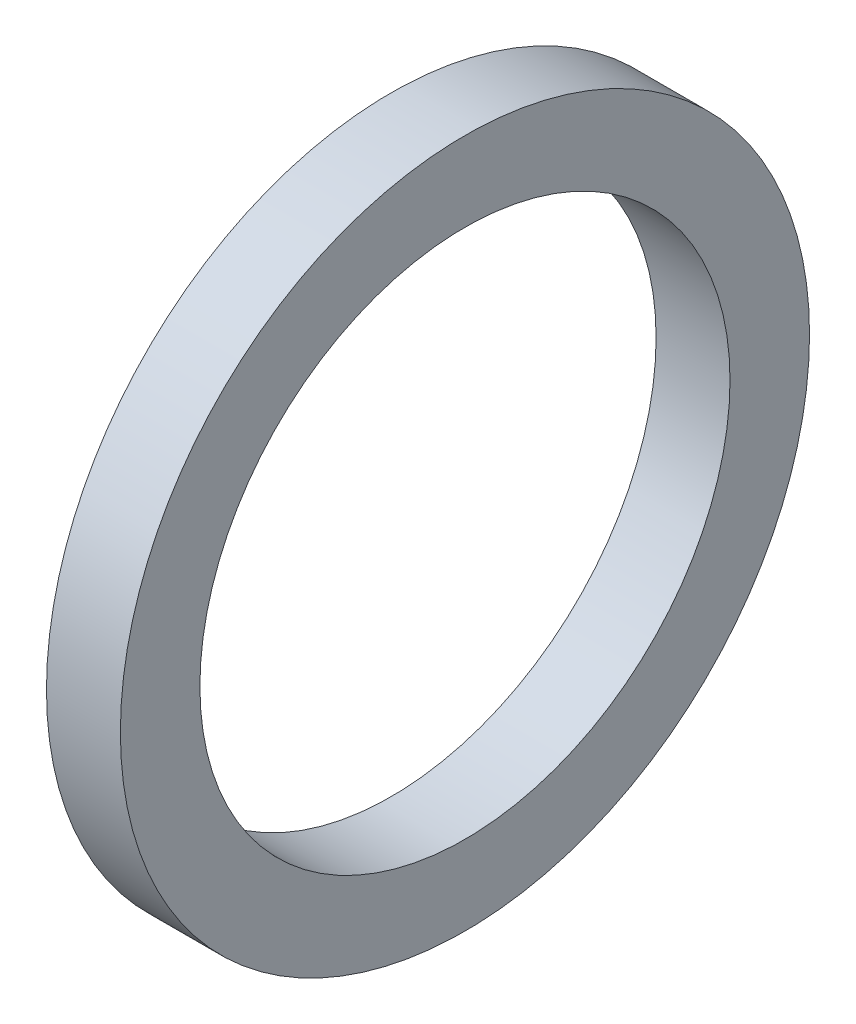
SolidWorks part; units mm, degrees
ref_plane "Front Plane" through (0, 0, 0) normal (0, 0, 1) x (1, 0, 0)
ref_plane "Top Plane" through (0, 0, 0) normal (0, 1, 0) x (1, 0, 0)
ref_plane "Right Plane" through (0, 0, 0) normal (1, 0, 0) x (0, 0, -1)
sketch "Sketch2" plane through (0, 0, 0) normal (0, 0, 1) x (1, 0, 0)
  line L0 (0, 0) -> (58.591, 0) construction
  line L2 (0, 0) -> (18.4, 0)
  line L3 (0, 0) -> (0, 2.5)
  line L4 (0, 2.5) -> (18.4, 2.5)
  line L5 (18.4, 0) -> (18.4, 2.5)
  line L6 (6, 2.5) -> (6, 6)
  line L11 (6, 6) -> (9.97, 6)
  line L16 (12.97, 6) -> (12.97, 3)
  line L17 (12.97, 3) -> (13.6304, 3)
  line L18 (13.6304, 3) -> (13.6304, 2.5)
  line L19 (13.6304, 2.5) -> (6, 2.5)
  line L22 (13.6304, 2.5) -> (16.1104, 2.5)
  line L23 (13.6304, 2.5) -> (13.6304, 4)
  line L24 (13.6304, 4) -> (16.1104, 4)
  line L25 (16.1104, 2.5) -> (16.1104, 4)
  line L27 (6, 6) -> (9.97, 6)
  line L28 (6, 6) -> (6, 9)
  line L29 (6, 9) -> (9.97, 9)
  line L30 (9.97, 6) -> (9.97, 9)
  line L31 (6, 9) -> (6, 8.25)
  line L32 (6, 8.25) -> (5, 8.25)
  line L33 (8.58, 22.001) -> (8.58, 12.476) construction
  line L34 (5, 12.476) -> (12.16, 12.476)
  line L35 (9.97, 9) -> (12.16, 9)
  line L36 (5, 7.5) -> (3, 7.5)
  line L37 (5, 8.25) -> (5, 12.476)
  line L38 (5, 7.5) -> (5, 14)
  line L39 (5, 14) -> (3, 14)
  line L40 (3, 7.5) -> (3, 14)
  line L41 (5, 22.001) -> (12.16, 22.001)
  line L42 (5, 22.001) -> (5, 30.1625)
  line L43 (5, 30.1625) -> (12.16, 30.1625)
  line L44 (12.16, 22.001) -> (12.16, 30.1625)
  line L49 (16.6304, 22.001) -> (16.6304, 7.5)
  line L51 (23.0104, 7.5) -> (23.0104, 6.5)
  line L54 (16.1104, 4) -> (13.6304, 4)
  line L56 (18.0304, 7.5) -> (23.0104, 7.5)
  line L57 (13.16, 22.001) -> (16.6304, 22.001)
  line L58 (16.1104, 3.5) -> (20.0104, 3.5)
  line L59 (29.9004, 14) -> (26.9004, 11)
  line L60 (4, 31.75) -> (18.0304, 31.75)
  line L61 (18.0304, 7.5) -> (23.0104, 7.5)
  line L62 (18.0304, 7.5) -> (18.0304, 12)
  line L63 (18.0304, 12) -> (23.0104, 12)
  line L64 (23.0104, 7.5) -> (23.0104, 12)
  line L65 (18.0304, 31.75) -> (18.0304, 12)
  line L66 (23.0104, 11) -> (26.9004, 11)
  line L67 (34.8004, 23) -> (31.3004, 19.5)
  line L68 (35.8004, 31) -> (38.7904, 33.99)
  line L69 (29.9004, 14) -> (29.9004, 15)
  line L70 (29.9004, 15) -> (22.9304, 15)
  line L71 (22.9304, 15) -> (21.0304, 15)
  line L72 (18.0304, 7.5) -> (16.6304, 7.5)
  line L73 (21.0304, 15) -> (21.0304, 43)
  line L74 (20.0304, 40) -> (10.0704, 40)
  line L75 (10.0704, 40) -> (4, 40)
  line L76 (21.0304, 43) -> (20.0304, 43)
  line L77 (22.9304, 15) -> (29.9004, 15)
  line L78 (22.9304, 15) -> (22.9304, 21)
  line L79 (22.9304, 21) -> (29.9004, 21)
  line L80 (29.9004, 15) -> (29.9004, 21)
  line L81 (10.0704, 40) -> (20.0304, 40)
  line L82 (10.0704, 40) -> (10.0704, 50)
  line L83 (10.0704, 50) -> (20.0304, 50)
  line L84 (20.0304, 40) -> (20.0304, 50)
  line L85 (4, 40) -> (4, 31.75)
  line L86 (12.97, 3) -> (12.97, 2.5)
  line L87 (31.3004, 19.5) -> (29.9004, 19.5)
  line L88 (21.51, 63.5) -> (21.51, 44)
  line L89 (21.51, 63.5) -> (25.9304, 63.5)
  line L90 (25.9304, 63.5) -> (25.9304, 25)
  line L91 (27.8304, 25) -> (25.9304, 25)
  line L92 (10.0704, 48) -> (9, 48)
  line L93 (9, 48) -> (9, 53.476)
  line L94 (9, 53.476) -> (20.0304, 53.476)
  line L95 (20.0304, 53.476) -> (20.0304, 50)
  line L96 (14.5152, 63.001) -> (14.5152, 53.476) construction
  line L97 (9, 63.001) -> (20.0304, 63.001)
  line L98 (9, 63.001) -> (9, 68.2625)
  line L99 (9, 68.2625) -> (20.0304, 68.2625)
  line L100 (20.0304, 63.001) -> (20.0304, 68.2625)
  line L101 (12.97, 6) -> (11.97, 6)
  line L102 (9, 42.5) -> (5, 42.5)
  line L103 (9, 42.5) -> (9, 55)
  line L104 (9, 55) -> (5, 55)
  line L105 (5, 42.5) -> (5, 55)
  line L106 (9.97, 6) -> (10.87, 6)
  line L107 (27.8304, 25) -> (34.8004, 25)
  line L108 (34.8004, 25) -> (34.8004, 23)
  line L109 (0, 0) -> (-2, 0)
  line L110 (0, 0) -> (0, 11)
  line L111 (27.8304, 25) -> (34.8004, 25)
  line L112 (27.8304, 25) -> (27.8304, 32.5)
  line L113 (27.8304, 32.5) -> (34.8004, 32.5)
  line L114 (34.8004, 25) -> (34.8004, 32.5)
  line L115 (35.8004, 31) -> (34.8004, 31)
  line L116 (27.8304, 32.5) -> (27.8304, 64.5)
  line L117 (21.1827, 74.025) -> (6.8477, 74.025)
  line L118 (6.8477, 74.025) -> (6.8477, 76.2)
  line L119 (38.7904, 47.29) -> (30.8304, 55.25)
  line L120 (0, 11) -> (-2, 11)
  line L121 (38.7904, 43.815) -> (30.8529, 43.815)
  line L123 (-4.8, 69.85) -> (1.55, 76.2)
  line L124 (38.7904, 47.29) -> (38.7904, 33.99)
  line L125 (-2, 0) -> (-2, 11)
  line L126 (38.7904, 37.465) -> (30.8529, 37.465)
  line L127 (30.8529, 43.815) -> (30.8529, 37.465)
  line L128 (6, 2.5) -> (6, 0)
  line L129 (0, 63.5) -> (0, 30)
  line L132 (5, 63.5) -> (0, 63.5)
  line L136 (-1.8, 30) -> (-11.76, 30)
  line L138 (-13.76, 25.4) -> (-2, 25.4)
  line L139 (-2, 25.4) -> (-2, 11.5)
  line L140 (27.8304, 64.5) -> (21.1827, 64.5)
  line L141 (-1.8, 30) -> (-11.76, 30)
  line L142 (-1.8, 30) -> (-1.8, 39)
  line L143 (-1.8, 39) -> (-11.76, 39)
  line L144 (-11.76, 30) -> (-11.76, 39)
  line L145 (21.1827, 64.5) -> (21.1827, 74.025)
  line L146 (-12.76, 37) -> (-12.76, 47.29)
  line L147 (-12.76, 37) -> (-11.76, 37)
  line L148 (30.8304, 55.25) -> (30.8304, 76.2)
  line L149 (11.97, 6) -> (11.97, 5.45)
  line L154 (-2, 11.5) -> (1, 11.5)
  line L155 (5, 60.6197) -> (24.05, 60.6197)
  line L160 (5, 60.6197) -> (5, 55.8572)
  line L161 (5, 55.8572) -> (24.05, 55.8572)
  line L166 (24.05, 60.6197) -> (24.05, 55.8572)
  line L167 (5, 60.6197) -> (24.05, 55.8572) construction
  line L172 (5, 55.8572) -> (24.05, 60.6197) construction
  line L173 (24.05, 62.2072) -> (25.9304, 62.2072)
  line L174 (11.97, 5.45) -> (10.87, 5.45)
  line L175 (10.87, 6) -> (10.87, 5.45)
  line L176 (24.05, 62.2072) -> (24.05, 54.2697)
  line L177 (24.05, 54.2697) -> (25.9304, 54.2697)
  line L178 (25.9304, 62.2072) -> (25.9304, 54.2697)
  line L179 (24.05, 62.2072) -> (25.9304, 54.2697) construction
  line L180 (24.05, 54.2697) -> (25.9304, 62.2072) construction
  line L181 (3, 19.6197) -> (15.7, 19.6197)
  line L182 (3, 19.6197) -> (3, 14.8572)
  line L183 (3, 14.8572) -> (15.7, 14.8572)
  line L184 (15.7, 19.6197) -> (15.7, 14.8572)
  line L185 (3, 19.6197) -> (15.7, 14.8572) construction
  line L186 (3, 14.8572) -> (15.7, 19.6197) construction
  line L187 (15.7, 21.2072) -> (16.6304, 21.2072)
  line L188 (15.7, 21.2072) -> (15.7, 13.2697)
  line L189 (15.7, 13.2697) -> (16.6304, 13.2697)
  line L190 (16.6304, 21.2072) -> (16.6304, 13.2697)
  line L191 (15.7, 21.2072) -> (16.6304, 13.2697) construction
  line L192 (15.7, 13.2697) -> (16.6304, 21.2072) construction
  line L193 (1, 11.5) -> (1, 6.5)
  line L194 (1, 6.5) -> (3, 6.5)
  line L195 (23.0104, 6.5) -> (20.0104, 3.5)
  line L196 (5, 63.5) -> (5, 42.5)
  line L197 (5, 42.5) -> (3, 42.5)
  line L198 (3, 42.5) -> (3, 6.5)
  line L199 (6, 0) -> (12.97, 0)
  line L200 (12.97, 0) -> (12.97, 2.5)
  line L201 (18.0304, 31.75) -> (18.0304, 35.875)
  line L202 (18.0304, 35.875) -> (21.0304, 35.875)
  line L203 (30.8304, 76.2) -> (6.8477, 76.2)
  line L204 (3.4027, 69.85) -> (7.8477, 69.85) construction
  line L205 (7.8477, 67.4687) -> (26.8977, 67.4688)
  line L206 (7.8477, 74.025) -> (7.8477, 64.5)
  line L207 (7.8477, 64.5) -> (-1.8, 64.5)
  line L208 (-1.8, 64.5) -> (-1.8, 39)
  line L209 (-12.76, 47.29) -> (-4.8, 55.25)
  line L210 (-4.8, 55.25) -> (-4.8, 69.85)
  line L211 (7.8477, 67.4687) -> (7.8477, 72.2313)
  line L212 (7.8477, 72.2313) -> (26.8977, 72.2313)
  line L213 (26.8977, 67.4688) -> (26.8977, 72.2313)
  line L214 (26.8977, 73.8187) -> (30.8304, 73.8187)
  line L215 (26.8977, 73.8187) -> (26.8977, 65.8813)
  line L216 (26.8977, 65.8813) -> (30.8304, 65.8813)
  line L217 (30.8304, 73.8187) -> (30.8304, 65.8813)
  line L218 (3.4027, 72.2313) -> (25.6277, 72.2313)
  line L219 (3.4027, 72.2313) -> (3.4027, 67.4687)
  line L220 (3.4027, 67.4687) -> (25.6277, 67.4687)
  line L221 (25.6277, 72.2313) -> (25.6277, 67.4687)
  line L222 (25.6277, 69.85) -> (21.1827, 69.85) construction
  line L223 (21.51, 44) -> (22.9304, 44)
  line L224 (22.9304, 44) -> (22.9304, 21)
  line L225 (13.6304, 4) -> (13.6304, 12.2697)
  line L226 (13.6304, 12.2697) -> (13.16, 12.2697)
  line L227 (13.16, 12.2697) -> (13.16, 22.001)
  line L228 (12.16, 9) -> (12.16, 12.476)
  line L229 (-1.8, 30) -> (0, 30)
  line L230 (9, 65.6317) -> (3.4027, 65.6317) construction
  line L231 (20.0304, 65.6317) -> (25.6277, 65.6317) construction
  line L232 (1.55, 76.2) -> (6.8477, 76.2)
  line L233 (-11.76, 30) -> (-13.76, 30)
  line L234 (-13.76, 30) -> (-13.76, 25.4)
  circle A0 centre (26.8804, 25.95) radius 0.95
  circle A1 centre (21.9804, 15.95) radius 0.95
  circle A2 centre (17.3304, 8.2) radius 0.7
  circle A3 centre (10.42, 6.45) radius 0.45
  circle A4 centre (-0.9, 30.9) radius 0.9
  point P7 (24.9902, 58.2385)
  point P131 (16.1652, 17.2385)
  point P135 (14.525, 58.2385)
  point P146 (9.35, 17.2385)
sketch "Sketch3" plane through (0, 0, 0) normal (0, 0, 1) x (1, 0, 0)
  line L0 (27.8304, 25) -> (34.8004, 25) construction
  line L1 (27.8304, 25) -> (27.8304, 32.5) construction
  line L2 (34.8004, 25) -> (34.8004, 32.5) construction
  line L3 (27.8304, 32.5) -> (34.8004, 32.5) construction
  line L4 (27.8304, 25) -> (34.8004, 25)
  line L5 (27.8304, 25) -> (27.8304, 32.5)
  line L6 (34.8004, 25) -> (34.8004, 32.5)
  line L7 (27.8304, 32.5) -> (34.8004, 32.5)
revolve "Revolve1" add sketch "Sketch3" angle 360 about L0
